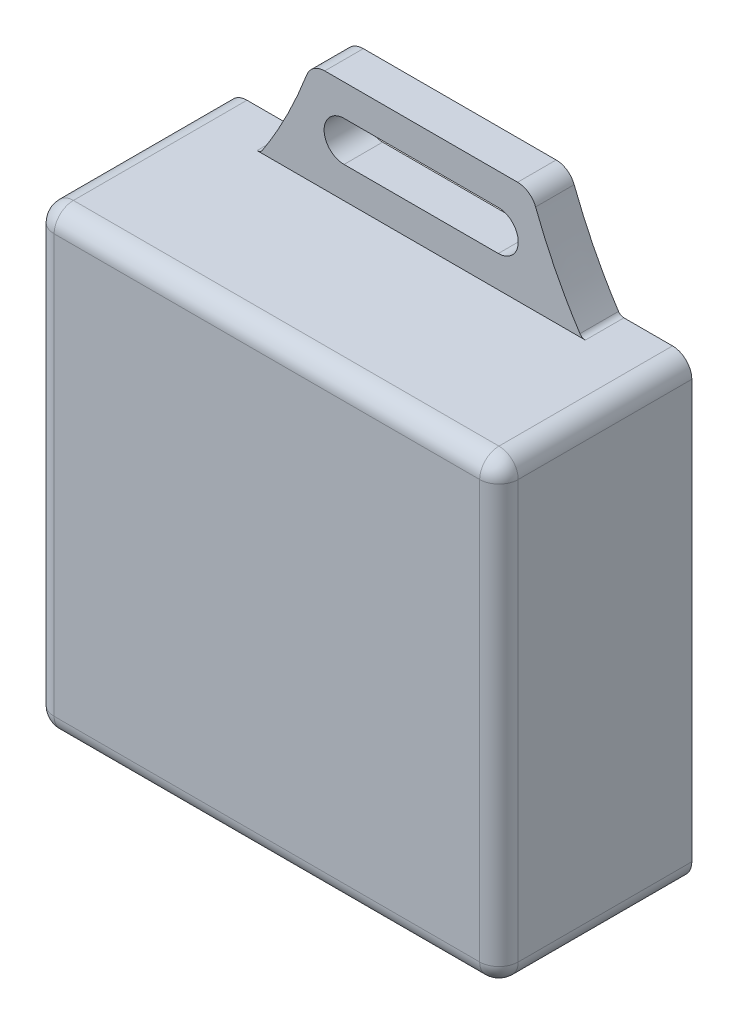
SolidWorks part; units mm, degrees
ref_plane "前视基准面" through (0, 0, 0) normal (0, 0, 1) x (1, 0, 0)
ref_plane "上视基准面" through (0, 0, 0) normal (0, 1, 0) x (1, 0, 0)
ref_plane "右视基准面" through (0, 0, 0) normal (1, 0, 0) x (0, 0, -1)
other "Configuration Table"
sketch "草图2" plane through (0, 0, 0) normal (0, 0, 1) x (1, 0, 0)
  line L0 (-7.5, 0) -> (7.5, 0)
  line L2 (12.5, -8) -> (16.55, -8)
  line L3 (18.05, -9.5) -> (18.05, -42)
  line L4 (18.05, -25.75) -> (-18.05, -25.75)
  line L5 (0, -51.5) -> (0, 0)
  line L6 (-7.5, 0) -> (7.5, 0)
  line L7 (-18.05, -9.5) -> (-18.05, -42)
  line L8 (-12.5, -8) -> (-16.55, -8)
  line L9 (-12.5, -43.5) -> (-16.55, -43.5)
  line L10 (-7.5, -51.5) -> (7.5, -51.5)
  line L11 (12.5, -43.5) -> (16.55, -43.5)
  line L12 (-7.5, -51.5) -> (7.5, -51.5)
  line L13 (0, 0) -> (0, -4)
  line L14 (-6, -4) -> (6, -4) construction
  line L15 (-6, -2.45) -> (6, -2.45)
  line L16 (-6, -5.55) -> (6, -5.55)
  line L17 (-6, -47.5) -> (6, -47.5) construction
  line L18 (-6, -49.05) -> (6, -49.05)
  line L19 (-6, -45.95) -> (6, -45.95)
  arc A0 (8.9005, -0.9628) -> (7.5, 0) centre (7.5, -1.5) ccw
  arc A1 (18.05, -9.5) -> (16.55, -8) centre (16.55, -9.5) ccw
  arc A2 (-18.05, -9.5) -> (-16.55, -8) centre (-16.55, -9.5) cw
  arc A3 (-8.9005, -0.9628) -> (-7.5, 0) centre (-7.5, -1.5) cw
  arc A4 (-8.9005, -50.5372) -> (-7.5, -51.5) centre (-7.5, -50) ccw
  arc A5 (-18.05, -42) -> (-16.55, -43.5) centre (-16.55, -42) ccw
  arc A6 (18.05, -42) -> (16.55, -43.5) centre (16.55, -42) cw
  arc A7 (8.9005, -50.5372) -> (7.5, -51.5) centre (7.5, -50) cw
  arc A8 (-6, -2.45) -> (-6, -5.55) centre (-6, -4) ccw
  arc A9 (6, -5.55) -> (6, -2.45) centre (6, -4) ccw
  arc A10 (-6, -49.05) -> (-6, -45.95) centre (-6, -47.5) cw
  arc A11 (6, -45.95) -> (6, -49.05) centre (6, -47.5) cw
  spline S0 degree 3 poles (8.9005, -0.9628) (9.8906, -3.544) (11.0905, -5.8897) (12.5, -8) knots 0.057327 0.057327 0.057327 0.057327 0.826257 0.826257 0.826257 0.826257
  spline S1 degree 3 poles (-8.9005, -0.9628) (-9.8906, -3.544) (-11.0905, -5.8897) (-12.5, -8) knots 0.057327 0.057327 0.057327 0.057327 0.826257 0.826257 0.826257 0.826257
  spline S2 degree 3 poles (-8.9005, -50.5372) (-9.8906, -47.956) (-11.0905, -45.6103) (-12.5, -43.5) knots 0.057327 0.057327 0.057327 0.057327 0.826257 0.826257 0.826257 0.826257
  spline S3 degree 3 poles (8.9005, -50.5372) (9.8906, -47.956) (11.0905, -45.6103) (12.5, -43.5) knots 0.057327 0.057327 0.057327 0.057327 0.826257 0.826257 0.826257 0.826257
  point P34 (0, -25.75)
  point P37 (0, -4)
  point P46 (0, -47.5)
  dimension "D1" = 1.5
  dimension "D5" = 1.5
  dimension "D6" = 3.1
  dimension "D2" = 18.05
  dimension "D3" = 8
  dimension "D4" = 25.75
  dimension "D7" = 12
  dimension "D8" = 4
extrude "凸台-拉伸1" add sketch "草图2" along normal blind 3 contours A3 S1 L8 A2 L7 L4 L5 L16 A8 L15 L13 L0 | S0 A0 L0 L13 L15 A9 L16 L5 L4 L3 A1 L2 | A7 S3 L11 A6 L3 L4 L5 L19 A11 L18 L10 | S2 A4 L10 L5 L18 A10 L19 L4 L7 A5 L9 region at (-8.5063, -14.9106, 0) region at (8.5063, -14.9106, 0) region at (-8.5063, -36.5894, 0) region at (8.5063, -36.5894, 0)
fillet "圆角1" radius 0.5 4 edges at (12.5, -43.5, 1.5) (-12.5, -43.5, 1.5) (-12.5, -8, 1.5) (12.5, -8, 1.5)
sketch "草图3" plane through (0, 0, 3) normal (0, 0, 1) x (1, 0, 0)
  line L0 (0, -8) -> (16.55, -8)
  line L1 (18.05, -9.5) -> (18.05, -42)
  line L2 (14.6593, -43.5) -> (16.55, -43.5)
  line L3 (12.7687, -43.5) -> (16.55, -43.5) construction
  line L4 (14.6593, -43.5) -> (-16.55, -43.5)
  line L5 (-18.05, -25.75) -> (-18.05, -42)
  line L6 (-18.05, -9.5) -> (-18.05, -42) construction
  line L7 (-18.05, -25.75) -> (-18.05, -9.5)
  line L8 (0, -8) -> (-16.55, -8)
  arc A0 (18.05, -9.5) -> (16.55, -8) centre (16.55, -9.5) ccw
  arc A1 (16.55, -43.5) -> (18.05, -42) centre (16.55, -42) ccw
  arc A2 (-18.05, -42) -> (-16.55, -43.5) centre (-16.55, -42) ccw
  arc A3 (-16.55, -8) -> (-18.05, -9.5) centre (-16.55, -9.5) ccw
extrude "凸台-拉伸2" add sketch "草图3" along normal blind 12
fillet "圆角2" radius 1.5 8 edges at (17.6107, -8.4393, 15) (18.05, -25.75, 15) (17.6107, -43.0607, 15) (0, -43.5, 15) (-17.6107, -43.0607, 15) (-18.05, -25.75, 15) (-17.6107, -8.4393, 15) (0, -8, 15)
sketch "草图4" plane through (-18.05, 0, 0) normal (-1, 0, 0) x (0, 0, 1)
  line L0 (15, -25.75) -> (7.5, -25.75)
  line L1 (15, -9.5) -> (15, -42) construction
  line L2 (8.25, -25.75) -> (8.25, -28.5)
  line L3 (6.5, -22.75) -> (8.5, -22.75)
  line L4 (6.5, -22.75) -> (6.5, -28.75)
  line L5 (6.5, -28.75) -> (8.5, -28.75)
  line L6 (8.5, -22.75) -> (8.5, -28.75)
  line L7 (6.5, -22.75) -> (8.5, -28.75) construction
  line L8 (6.5, -28.75) -> (8.5, -22.75) construction
  line L9 (7.5, -25.75) -> (8.25, -25.75)
  line L10 (8.25, -28.5) -> (6.75, -28.5)
  line L11 (6.75, -28.5) -> (6.75, -25.75)
  line L12 (6.75, -25.75) -> (7.5, -25.75)
  dimension "D1" = 7.5
  dimension "D2" = 6
  dimension "D3" = 2
extrude "切除-拉伸1" cut sketch "草图4" against normal blind 4 contours L11 L12 L0 L6 L3 L4 L5 L2 L10 | L12 L11 L10 L2 L0 region at (-18.05, -27.125, 7.5) region at (-18.05, -25.0298, 7.5)
extrude "凸台-拉伸3" add sketch "草图4<3>" against normal blind 4 and the other way blind 2 contours L12 L11 L10 L2 L0 region at (-18.05, -27.125, 7.5)
sketch "草图4<3>" plane through (-18.05, 0, 0) normal (-1, 0, 0) x (0, 0, 1) same geometry as "草图4"
